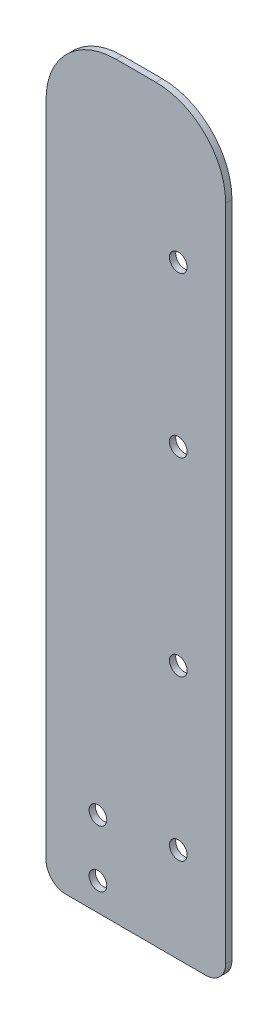
SolidWorks part; units mm, degrees
ref_plane "Front Plane" through (0, 0, 0) normal (0, 0, 1) x (1, 0, 0)
ref_plane "Top Plane" through (0, 0, 0) normal (0, 1, 0) x (1, 0, 0)
ref_plane "Right Plane" through (0, 0, 0) normal (1, 0, 0) x (0, 0, -1)
sketch "Sketch1" plane through (0, 0, 0) normal (0, 0, 1) x (1, 0, 0)
  line L1 (0, -146.6506) -> (0, 146.6506) construction
  line L3 (45.72, 5.08) -> (45.72, 172.72)
  line L5 (40.64, 0) -> (33.655, 0)
  line L7 (66.681, 0) -> (66.681, 88.9) construction
  line L8 (33.655, 0) -> (45.72, 0) construction
  line L9 (33.655, 177.8) -> (33.655, 0) construction
  line L10 (118.1346, 0) -> (-118.1346, 0) construction
  line L11 (66.681, 88.9) -> (0, 88.9) construction
  line L14 (33.655, 0) -> (5.07, 0.0545)
  line L18 (66.681, 88.9) -> (66.681, 177.8) construction
  line L19 (66.681, 177.8) -> (0, 177.8) construction
  line L20 (0, 5.08) -> (0, 172.72)
  line L23 (33.655, 0) -> (25.4, 0.0158) construction
  line L24 (13.208, 7.151) -> (13.208, 0.039) construction
  line L25 (25.4, 0.0158) -> (19.812, 0.0264) construction
  line L26 (19.812, 0.0264) -> (19.812, 8.89) construction
  line L27 (19.812, 8.89) -> (19.812, 177.8) construction
  line L28 (33.655, 24.13) -> (0, 24.13) construction
  line L35 (25.4, 0.0158) -> (22.7313, 0.0208) construction
  line L36 (66.681, 0) -> (0, 0) construction
  line L46 (17.78, 190.5) -> (27.94, 190.5)
  line L47 (19.9023, 177.8) -> (19.9023, 190.5) construction
  line L48 (20.4442, 160.274) -> (19.9023, 190.5) construction
  line L49 (19.9023, 190.5) -> (-14.4304, 190.5) construction
  line L50 (20.4442, 160.274) -> (0, 160.274) construction
  line L51 (45.72, 10.2129) -> (43.18, 10.2129) construction
  line L52 (43.18, 10.2129) -> (43.18, 0.6806) construction
  line L53 (43.18, 0.6806) -> (43.18, 181.8781) construction
  line L54 (13.208, 0.039) -> (13.208, 189.9021) construction
  circle A0 centre (33.655, 24.13) radius 2.2479
  circle A1 centre (33.655, 64.77) radius 2.2479
  arc A5 (40.64, 0) -> (45.72, 5.08) centre (40.64, 5.08) ccw
  arc A6 (5.07, 0.0545) -> (0, 5.08) centre (5.0797, 5.1345) cw
  circle A7 centre (33.655, 113.03) radius 2.2479
  circle A8 centre (33.655, 153.67) radius 2.2479
  arc A13 (45.72, 172.72) -> (27.94, 190.5) centre (27.94, 172.72) ccw
  arc A14 (0, 172.72) -> (17.78, 190.5) centre (17.78, 172.72) cw
  circle A15 centre (13.208, 7.151) radius 2.2479
  circle A16 centre (13.208, 21.6291) radius 2.2479
  point P24 (0, 190.5)
  point P30 (0, 0)
  point P38 (0, 190.5)
  point P42 (0, 185.42)
  point P46 (40.64, 185.0608)
  point P52 (0, 190.5)
  dimension "D7" = 4.4958
  dimension "D5" = 24.13
  dimension "D6" = 4.4958
  dimension "D9" = 24.13
  dimension "D11" = 88.9
  dimension "D12" = 5.08
  dimension "D13" = 4.4958
  dimension "D15" = 4.4958
  dimension "D17" = 4.4958
  dimension "D19" = 17.78
  dimension "D22" = 15.24
  dimension "D26" = 2.54
  dimension "D20" = 32.512
  dimension "D25" = 12.7
  dimension "D27" = 9.525
  dimension "D23" = 4.4958
  dimension "D1" = 190.5
  dimension "D2" = 45.72
  dimension "D3" = 88.9
  dimension "D4" = 9.525
  dimension "D8" = 40.64
  dimension "D10" = 24.13
  dimension "D14" = 7.112
  dimension "D16" = 40.64
  dimension "D18" = 24.13
  dimension "D21" = 30.226
  dimension "D24" = 21.59
  dimension "D28" = 64.77
extrude "Boss-Extrude2" add sketch "Sketch1" along normal blind 1.6002
